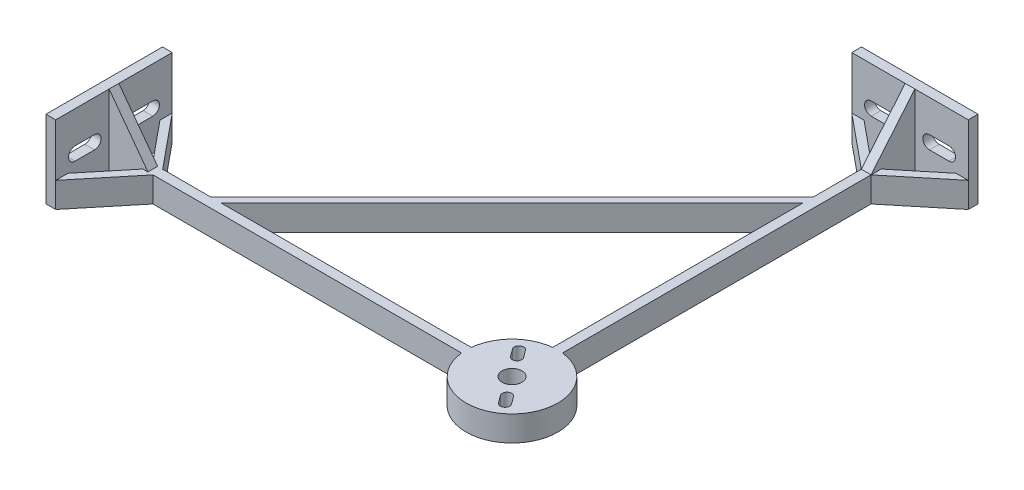
SolidWorks part; units mm, degrees
material "ABS"
ref_plane "Front Plane" through (0, 0, 0) normal (0, 0, 1) x (1, 0, 0)
ref_plane "Top Plane" through (0, 0, 0) normal (0, 1, 0) x (1, 0, 0)
ref_plane "Right Plane" through (0, 0, 0) normal (1, 0, 0) x (0, 0, -1)
sketch "Sketch1" plane through (0, 0, 0) normal (0, 1, 0) x (1, 0, 0)
  line L0 (-1.5875, 14.9158) -> (-1.5875, 130.175)
  line L1 (1.5875, 130.175) -> (1.5875, 14.9158)
  line L2 (-1.5875, 130.175) -> (1.5875, 130.175)
  line L4 (-14.9158, -1.5875) -> (-130.175, -1.5875)
  line L5 (-130.175, -1.5875) -> (-130.175, 1.5875)
  line L8 (-130.175, 1.5875) -> (-14.9158, 1.5875)
  line L9 (0, 0) -> (-130.175, 0) construction
  line L11 (0, 0) -> (0, 146.05) construction
  circle A0 centre (0, 0) radius 15
  point P19 (0, 0)
  point P21 (0, 0)
  dimension "D1" = 30
  dimension "D2" = 3.175
  dimension "D4" = 1.5875
  dimension "D3" = 2
  dimension "D5" = 130.175
extrude "Boss-Extrude2" add sketch "Sketch1" along normal blind 8.255 contours A0
extrude "Boss-Extrude3" add sketch "Sketch1<6>" along normal blind 8.255 contours L4 A0 | A0 | A0 region at (0, 0, -72.5735) region at (-72.5735, 0, 0)
sketch "Sketch1<6>" plane through (0, 0, 0) normal (0, 1, 0) x (1, 0, 0) same geometry as "Sketch1"
sketch "Sketch5" plane through (0, 8.255, 0) normal (0, 1, 0) x (1, 0, 0)
  line L0 (0, 0) -> (130.175, 0) construction
  line L1 (0, 0) -> (0, -22.3627) construction
  line L2 (-6.4967, 8.7797) -> (0, 0) construction
  line L3 (-4.6836, 6.3296) -> (-6.4967, 8.7797) construction
  line L4 (-5.9087, 5.4231) -> (-7.7217, 7.8732)
  line L5 (-3.4586, 7.2361) -> (-5.2716, 9.6862)
  line L6 (0, 0) -> (1.0099, 0.7473) construction
  line L7 (4.6836, -6.3296) -> (6.4967, -8.7797) construction
  line L8 (3.4586, -7.2361) -> (5.2716, -9.6862)
  line L9 (5.9087, -5.4231) -> (7.7217, -7.8732)
  line L10 (-1.5875, 130.175) -> (1.5875, 130.175) construction
  arc A0 (3.4586, -7.2361) -> (5.9087, -5.4231) centre (4.6836, -6.3296) cw
  arc A1 (-5.9087, 5.4231) -> (-3.4586, 7.2361) centre (-4.6836, 6.3296) ccw
  arc A2 (-5.2716, 9.6862) -> (-7.7217, 7.8732) centre (-6.4967, 8.7797) ccw
  arc A3 (7.7217, -7.8732) -> (5.2716, -9.6862) centre (6.4967, -8.7797) cw
  circle A6 centre (0, 0) radius 3.25
  point P8 (-5.5901, 7.5546)
  point P17 (5.5901, -7.5546)
  point P18 (0, 0)
  point P25 (-8.4173, 4.1799)
  dimension "D3" = 3.048
  dimension "D1" = 7.874
  dimension "D2" = 3.048
  dimension "D4" = 53.5
extrude "Cut-Extrude3" cut sketch "Sketch5" against normal blind 63.5
ref_axis "Axis1" through (0, 0, 0) along (0, 1, 0)
ref_plane "Plane1" through (0, 0, 0) normal (0, 0, 1) x (1, 0, 0)
ref_plane "Plane2" through (0, 0, 0) normal (1, 0, 0) x (0, 0, -1)
sketch "Sketch7" plane through (0, 0, 0) normal (1, 0, 0) x (0, 0, -1)
  line L1 (130.175, 0) -> (133.35, 0)
  line L2 (130.175, 0) -> (130.175, 25.4)
  line L3 (130.175, 25.4) -> (133.35, 25.4)
  line L4 (133.35, 0) -> (133.35, 25.4)
  dimension "D1" = 3.175
  dimension "D2" = 25.4
extrude "Boss-Extrude5" add sketch "Sketch7" along normal blind 19.05 and the other way blind 19.05
sketch "Sketch8" plane through (-19.05, 0, 0) normal (-1, 0, 0) x (0, 0, 1)
  line L1 (-133.35, 0) -> (-130.175, 0)
  line L2 (-133.35, 0) -> (-133.35, 25.4)
  line L3 (-133.35, 25.4) -> (-130.175, 25.4)
  line L4 (-130.175, 0) -> (-130.175, 25.4)
sketch "Sketch12" plane through (0, 0, -133.35) normal (0, 0, -1) x (-1, 0, 0)
  line L0 (-19.05, 12.7) -> (19.05, 12.7) construction
  line L1 (-19.05, 0) -> (-19.05, 25.4) construction
  line L2 (19.05, 0) -> (19.05, 25.4) construction
  line L3 (-6.35, 12.7) -> (-12.7, 12.7) construction
  line L4 (-6.35, 10.541) -> (-12.7, 10.541)
  line L5 (-6.35, 14.859) -> (-12.7, 14.859)
  line L6 (6.35, 12.7) -> (12.7, 12.7) construction
  line L7 (6.35, 14.859) -> (12.7, 14.859)
  line L8 (6.35, 10.541) -> (12.7, 10.541)
  line L9 (0, 12.7) -> (0, 25.4) construction
  line L10 (19.05, 25.4) -> (-19.05, 25.4) construction
  arc A0 (-6.35, 10.541) -> (-6.35, 14.859) centre (-6.35, 12.7) ccw
  arc A1 (-12.7, 14.859) -> (-12.7, 10.541) centre (-12.7, 12.7) ccw
  arc A2 (6.35, 14.859) -> (6.35, 10.541) centre (6.35, 12.7) ccw
  arc A3 (12.7, 10.541) -> (12.7, 14.859) centre (12.7, 12.7) ccw
  point P8 (-9.525, 12.7)
  point P13 (9.525, 12.7)
  dimension "D1" = 6.35
  dimension "D2" = 4.318
  dimension "D3" = 4.318
  dimension "D4" = 6.35
  dimension "D5" = 9.525
  dimension "D6" = 9.525
extrude "Cut-Extrude6" cut sketch "Sketch12" against normal through all
pattern_circular "CirPattern2" count 2 every 90 about axis through (0, 0, 0) along (0, 1, 0) of "Boss-Extrude5"
pattern_circular "CirPattern3" count 2 every 90 about axis through (0, 0, 0) along (0, 1, 0) of "Cut-Extrude6"
sketch "Sketch13" plane through (0, 0, 0) normal (0, -1, 0) x (1, 0, 0)
  line L0 (-96.6289, -1.5875) -> (-1.5875, -96.6289)
  line L1 (-130.175, -1.5875) -> (-14.9158, -1.5875) construction
  line L2 (-1.5875, -14.9158) -> (-1.5875, -130.175) construction
  line L3 (-100.2211, -1.5875) -> (-1.5875, -100.2211)
  line L4 (-96.6289, -1.5875) -> (-100.2211, -1.5875)
  line L5 (-1.5875, -100.2211) -> (-1.5875, -96.6289)
  line L6 (-19.05, -130.175) -> (-1.5875, -130.175) construction
  line L7 (-130.175, -1.5875) -> (-130.175, -19.05) construction
  line L8 (-19.05, -130.175) -> (-1.5875, -115.8315)
  line L9 (-1.5875, -115.8315) -> (-1.5875, -119.1185)
  line L10 (-1.5875, -119.1185) -> (-15.0482, -130.175)
  line L11 (-15.0482, -130.175) -> (-19.05, -130.175)
  line L12 (19.05, -130.175) -> (1.5875, -115.8315)
  line L13 (1.5875, -130.175) -> (1.5875, -14.9158) construction
  line L14 (1.5875, -115.8315) -> (1.5875, -119.1185)
  line L15 (1.5875, -119.1185) -> (15.0482, -130.175)
  line L16 (1.5875, -130.175) -> (19.05, -130.175) construction
  line L17 (15.0482, -130.175) -> (19.05, -130.175)
  line L18 (-119.1185, 1.5875) -> (-130.175, 15.0482)
  line L19 (-130.175, 19.05) -> (-115.8315, 1.5875)
  line L20 (-130.175, 15.0482) -> (-130.175, 19.05)
  line L21 (-119.1185, -1.5875) -> (-130.175, -15.0482)
  line L22 (-130.175, -19.05) -> (-115.8315, -1.5875)
  line L23 (-115.8315, -1.5875) -> (-119.1185, -1.5875)
  line L24 (-115.8315, 1.5875) -> (-119.1185, 1.5875)
  line L25 (-130.175, -15.0482) -> (-130.175, -19.05)
  point P8 (-1.5875, -72.5454)
  point P9 (-1.5875, -98.425)
  point P12 (-98.425, -1.5875)
  point P25 (-1.5875, -117.475)
  point P30 (1.5875, -117.475)
  point P42 (0, 0)
  dimension "D1" = 31.75
  dimension "D2" = 31.75
  dimension "D3" = 2.54
  dimension "D4" = 2.54
  dimension "D5" = 2.54
  dimension "D6" = 12.7
  dimension "D7" = 2
extrude "Boss-Extrude6" add sketch "Sketch13" against normal up to surface (8.255 mm away) up to face at (0, 8.255, 3.25)
sketch "Sketch14" plane through (0, 0, 0) normal (0, 0, 1) x (1, 0, 0)
  line L0 (-130.175, 25.4) -> (-117.475, 8.255)
  line L1 (-14.9158, 8.255) -> (-115.8315, 8.255) construction
  line L2 (-117.475, 8.255) -> (-130.175, 8.255)
  line L3 (-130.175, 8.255) -> (-130.175, 25.4)
  dimension "D1" = 12.7
extrude "Boss-Extrude7" add sketch "Sketch14" along normal up to surface and the other way up to surface up to face at (-124.6467, 4.1275, 1.5875) other way up to face at (-124.6467, 4.1275, -1.5875)
sketch "Sketch15" plane through (0, 0, 0) normal (1, 0, 0) x (0, 0, -1)
  line L0 (130.175, 25.4) -> (115.8315, 8.255)
  line L1 (115.8315, 8.255) -> (115.8315, 0) construction
  line L2 (130.175, 8.255) -> (115.8315, 8.255) construction
  line L3 (115.8315, 8.255) -> (130.175, 8.255)
  line L4 (130.175, 8.255) -> (130.175, 25.4)
extrude "Boss-Extrude8" add sketch "Sketch15" along normal up to surface and the other way up to surface up to face at (1.5875, 4.1275, -65.3736) other way up to face at (-1.5875, 4.1275, -108.0263)
